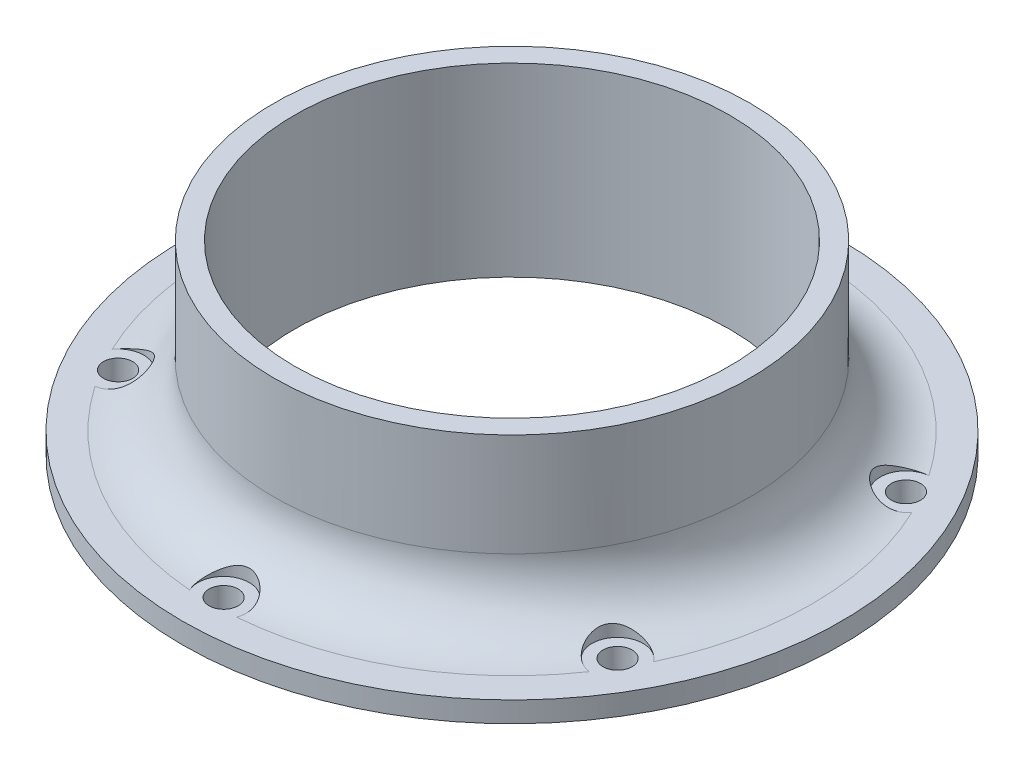
SolidWorks part; units mm, degrees
material "6061 Alloy"
ref_plane "Front Plane" through (0, 0, 0) normal (0, 0, 1) x (1, 0, 0)
ref_plane "Top Plane" through (0, 0, 0) normal (0, 1, 0) x (1, 0, 0)
ref_plane "Right Plane" through (0, 0, 0) normal (1, 0, 0) x (0, 0, -1)
sketch "Sketch1" plane through (0, 0, 0) normal (0, 1, 0) x (1, 0, 0)
  circle A0 centre (0, 0) radius 33.528
  circle A1 centre (0, 0) radius 36.703
  dimension "D1" = 67.056
  dimension "D2" = 3.175
extrude "Boss-Extrude1" add sketch "Sketch1" along normal blind 25.4
sketch "Sketch2" plane through (0, 0, 0) normal (0, -1, 0) x (1, 0, 0)
  circle A0 centre (0, 0) radius 33.528
  circle A1 centre (0, 0) radius 50.8
  circle A2 centre (0, 0) radius 33.528 construction
  dimension "D1" = 101.6
extrude "Boss-Extrude2" add sketch "Sketch2" along normal blind 3.175
fillet "Fillet1" radius 9.525 1 edges at (0, 0, -36.703)
hole_wizard "#8 Clearance Hole1" positions "Sketch4" profile "Sketch5" hole size "#8" standard "Ansi Inch" end condition through all
sketch "Sketch4" plane through (0, 0, 0) normal (0, 1, 0) x (-1, 0, 0)
  point P0 (0, -44.45)
  dimension "D1" = 44.45
sketch "Sketch5" plane through (0, 0, -44.45) normal (1, 0, 0) x (0, 0, 1)
  line L0 (0, 0) -> (0, 3.175)
  line L1 (0, 3.175) -> (2.2479, 3.175)
  line L2 (2.2479, 3.175) -> (2.2479, 0)
  line L5 (2.2479, 0) -> (0, 0)
  line L11 (0, -6.35) -> (0, 107.95) construction
  dimension "Thru Hole Dia." = 4.4958
  dimension "Thru Hole Depth" = 3.175
pattern_circular "CirPattern1" count 6 over 360 about axis through (0, 25.4, 0) along (0, -1, 0) of "#8 Clearance Hole1"
sketch "Sketch6" plane through (0, 0, 0) normal (0, 1, 0) x (1, 0, 0)
  circle A0 centre (0, 44.45) radius 3.9624
  dimension "D1" = 7.9248
extrude "Cut-Extrude1" cut sketch "Sketch6" along normal blind 52.07
pattern_circular "CirPattern2" count 6 over 360 about axis through (0, -3.175, 0) along (0, 1, 0) of "Cut-Extrude1"
